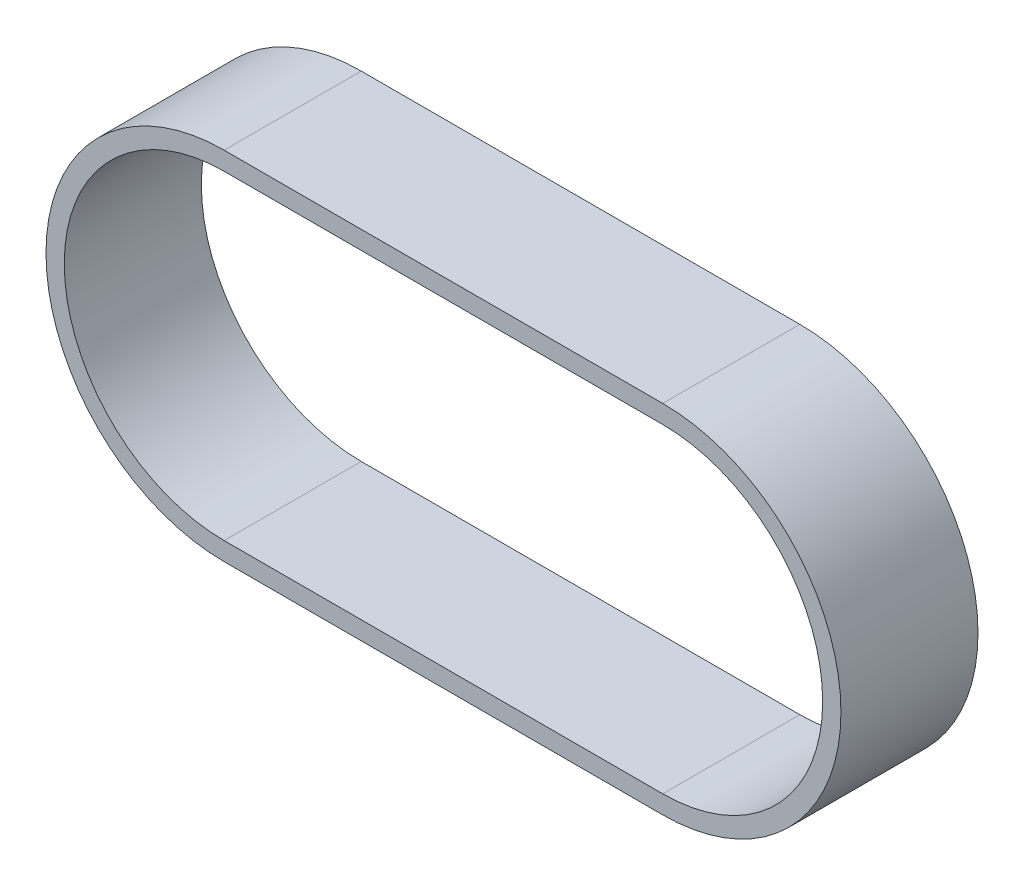
SolidWorks part; units mm, degrees
material "Silicon Rubber"
ref_plane "Front Plane" through (0, 0, 0) normal (0, 0, 1) x (1, 0, 0)
ref_plane "Top Plane" through (0, 0, 0) normal (0, 1, 0) x (1, 0, 0)
ref_plane "Right Plane" through (0, 0, 0) normal (1, 0, 0) x (0, 0, -1)
sketch "Sketch1" plane through (0, 0, 0) normal (0, 0, 1) x (1, 0, 0)
  line L0 (-20.3819, 0) -> (25.0953, 0) construction
  line L1 (-24, 17.5) -> (24, 17.5)
  line L2 (0, 23.3367) -> (0, -30.4014) construction
  line L3 (-24, -17.5) -> (24, -17.5)
  line L4 (-24, 19.5) -> (24, 19.5)
  line L5 (-24, -19.5) -> (24, -19.5)
  arc A0 (-24, -17.5) -> (-24, 17.5) centre (-24, 0) cw
  arc A1 (24, 17.5) -> (24, -17.5) centre (24, 0) cw
  arc A2 (24, 19.5) -> (24, -19.5) centre (24, 0) cw
  arc A3 (-24, -19.5) -> (-24, 19.5) centre (-24, 0) cw
  dimension "D2" = 17.5
  dimension "D1" = 48
  dimension "D3" = 2
extrude "Boss-Extrude1" add sketch "Sketch1" along normal blind 7.5 and the other way blind 7.5
